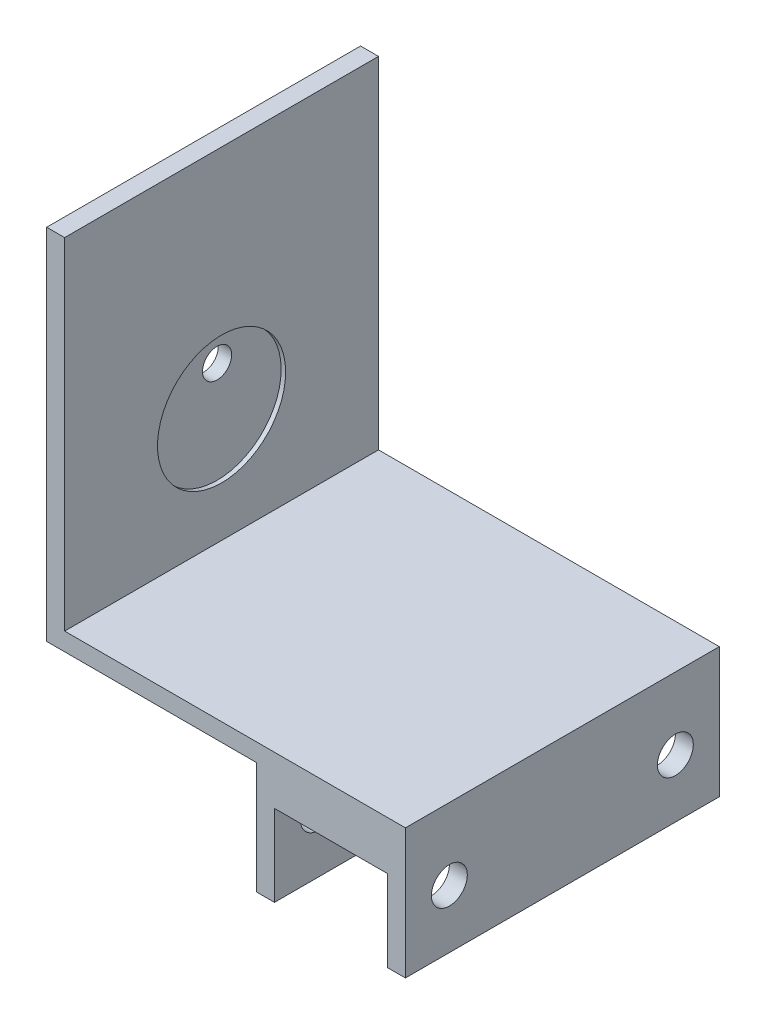
SolidWorks part; units mm, degrees
ref_plane "Front Plane" through (0, 0, 0) normal (0, 0, 1) x (1, 0, 0)
ref_plane "Top Plane" through (0, 0, 0) normal (0, 1, 0) x (1, 0, 0)
ref_plane "Right Plane" through (0, 0, 0) normal (1, 0, 0) x (0, 0, -1)
sketch "Sketch1" plane through (0, 0, 0) normal (0, 1, 0) x (1, 0, 0)
  line L0 (4, 70) -> (4, 0)
  line L1 (0, 0) -> (80, 0)
  line L2 (0, 0) -> (0, 70)
  line L3 (0, 70) -> (80, 70)
  line L4 (80, 0) -> (80, 70)
  line L5 (76, 70) -> (76, 0)
  line L6 (50.8, 70) -> (50.8, 0)
  line L7 (46.8, 70) -> (46.8, 0)
  dimension "D1" = 70
  dimension "D2" = 80
  dimension "D3" = 4
  dimension "D4" = 4
  dimension "D5" = 4
  dimension "D6" = 25.2
extrude "Boss-Extrude1" add sketch "Sketch1" along normal blind 4 contours L1 L4 L3 L0 | L2 L1 L4 L3 region at (25.4, 0, -35)
extrude "Boss-Extrude2" add sketch "Sketch1<3>" along normal blind 80 contours L3 L2 L1 L0 region at (2, 0, -35)
sketch "Sketch1<3>" plane through (0, 0, 0) normal (0, 1, 0) x (1, 0, 0) same geometry as "Sketch1"
extrude "Boss-Extrude3" add sketch "Sketch1<4>" against normal blind 25 contours L3 L5 L1 L4 | L3 L7 L1 L6 region at (48.8, 0, -35) region at (78, 0, -35)
sketch "Sketch1<4>" plane through (0, 0, 0) normal (0, 1, 0) x (1, 0, 0) same geometry as "Sketch1"
sketch "Sketch2" plane through (80, 0, 0) normal (1, 0, 0) x (0, 0, -1)
  line L0 (35, 4) -> (35, -25) construction
  line L4 (0, 4) -> (0, -25)
  line L5 (0, -25) -> (70, -25)
  line L6 (70, -25) -> (70, 4)
  line L7 (70, 4) -> (0, 4)
  line L8 (0, 4) -> (0, -25)
  line L9 (0, -25) -> (70, -25)
  line L10 (70, -25) -> (70, 4)
  line L11 (70, 4) -> (0, 4)
  circle A1 centre (60.2, -12) radius 4
  circle A2 centre (9.8, -12) radius 4
  dimension "D3" = 8
  dimension "D4" = 13
  dimension "D6" = 9.8
  dimension "D1" = 0
extrude "Cut-Extrude1" cut sketch "Sketch2" against normal through all contours A2 | A1 region at (80, -12, -60.2) region at (80, -12, -9.8)
sketch "Sketch3" plane through (4, 0, 0) normal (1, 0, 0) x (0, 0, -1)
  line L0 (0, 80) -> (70, 4) construction
  line L1 (0, 4) -> (70, 80) construction
  line L4 (0, 80) -> (0, 4)
  line L5 (0, 4) -> (70, 4)
  line L6 (70, 4) -> (70, 80)
  line L7 (70, 80) -> (0, 80)
  line L8 (0, 80) -> (0, 4)
  line L9 (0, 4) -> (70, 4)
  line L10 (70, 4) -> (70, 80)
  line L11 (70, 80) -> (0, 80)
  circle A0 centre (35, 29.4) radius 25.4
  circle A1 centre (35, 37.756) radius 3.25
  circle A2 centre (35, 29.4) radius 14.2875
  point P8 (0, 0)
  point P10 (35, 42)
  dimension "D2" = 50.8
  dimension "D4" = 6.5
  dimension "D5" = 28.575
  dimension "D3" = 8.356
  dimension "D1" = 0
extrude "Cut-Extrude2" cut sketch "Sketch3" against normal through all contours A1 region at (4, 37.756, -35)
extrude "Cut-Extrude3" cut sketch "Sketch3<3>" against normal blind 1 contours A2 A1 region at (4, 28.944, -35)
sketch "Sketch3<3>" plane through (4, 0, 0) normal (1, 0, 0) x (0, 0, -1) same geometry as "Sketch3"
extrude "Boss-Extrude4" add sketch "Sketch1<5>" against normal blind 6.84 contours L3 L6 L1 L5 region at (63.4, 0, -35)
sketch "Sketch1<5>" plane through (0, 0, 0) normal (0, 1, 0) x (1, 0, 0) same geometry as "Sketch1"
